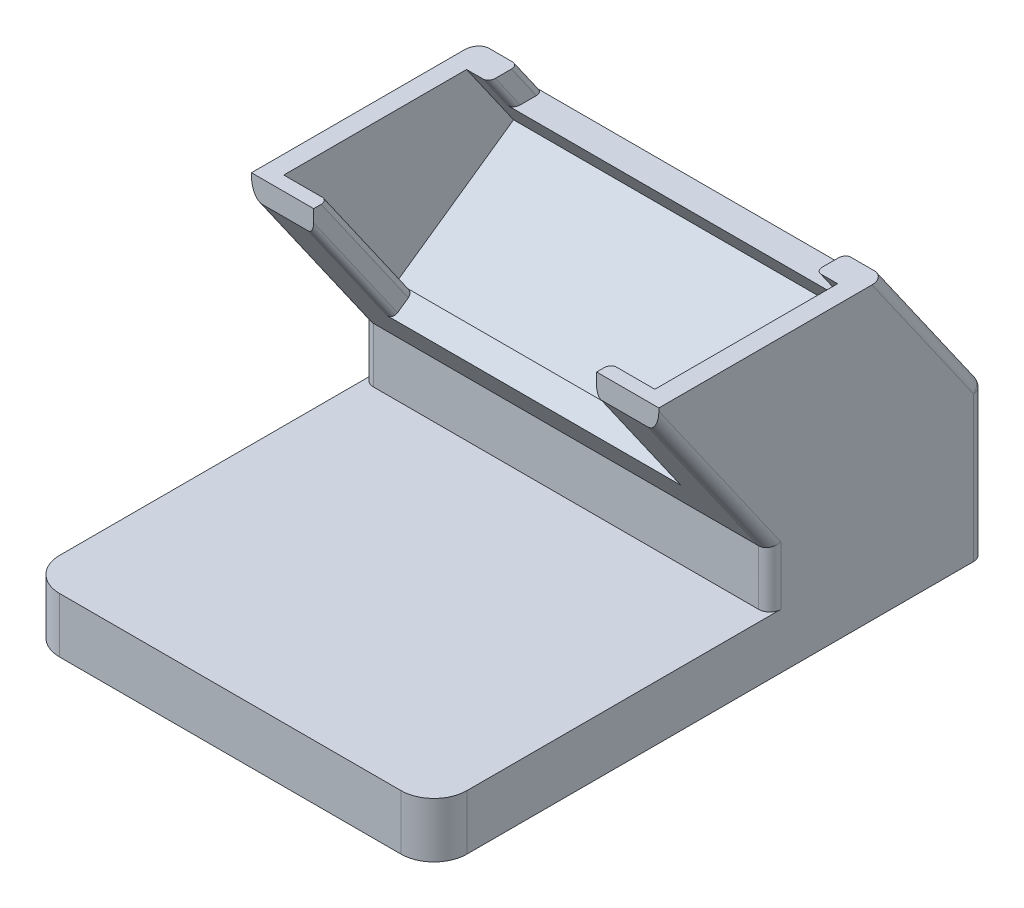
SolidWorks part; units mm, degrees
ref_plane "前视基准面" through (0, 0, 0) normal (0, 0, 1) x (1, 0, 0)
ref_plane "上视基准面" through (0, 0, 0) normal (0, 1, 0) x (1, 0, 0)
ref_plane "右视基准面" through (0, 0, 0) normal (1, 0, 0) x (0, 0, -1)
sketch "草图1" plane through (0, 0, 0) normal (1, 0, 0) x (0, 0, -1)
  line L0 (0, 0) -> (0, 5)
  line L1 (0, 5) -> (30.4974, 5)
  line L2 (30.4974, 5) -> (30.4974, 10)
  line L3 (30.4974, 10) -> (19.0259, 26.383)
  line L4 (19.0259, 26.383) -> (33.7706, 36.7074)
  line L5 (33.7706, 36.7074) -> (50, 13.5294)
  line L6 (50, 13.5294) -> (50, 0)
  line L7 (50, 0) -> (0, 0)
  dimension "D1" = 18
  dimension "D2" = 5
  dimension "D3" = 5
  dimension "D4" = 20
  dimension "D5" = 50
  dimension "D6" = 55
extrude "凸台-拉伸1" add sketch "草图1" along normal blind 37
sketch "草图2" plane through (0, 8.7641, 6.1367) normal (0, 0.8192, 0.5736) x (1, 0, 0)
  line L0 (18.5, 48.7178) -> (18.5, 30.7178) construction
  line L1 (37, 48.7178) -> (0, 48.7178) construction
  line L2 (37, 30.7178) -> (0, 30.7178) construction
  line L3 (0, 39.7178) -> (37, 39.7178) construction
  line L4 (0, 48.7178) -> (0, 30.7178) construction
  line L5 (37, 48.7178) -> (37, 30.7178) construction
  line L6 (33.35, 48.7178) -> (3.65, 48.7178)
  line L7 (3.65, 48.7178) -> (3.65, 46.5178)
  line L8 (3.65, 46.5178) -> (1.65, 46.5178)
  line L9 (1.65, 46.5178) -> (1.65, 32.9178)
  line L10 (1.65, 32.9178) -> (5.65, 32.9178)
  line L11 (5.65, 32.9178) -> (5.65, 30.7178)
  line L12 (37, 30.7178) -> (0, 30.7178) construction
  line L13 (5.65, 30.7178) -> (31.35, 30.7178)
  line L14 (31.35, 32.9178) -> (31.35, 30.7178)
  line L15 (35.35, 32.9178) -> (31.35, 32.9178)
  line L16 (33.35, 46.5178) -> (35.35, 46.5178)
  line L17 (35.35, 46.5178) -> (35.35, 32.9178)
  line L18 (33.35, 48.7178) -> (33.35, 46.5178)
  dimension "D1" = 13.6
  dimension "D2" = 2.2
  dimension "D3" = 2.2
  dimension "D4" = 33.7
  dimension "D5" = 4
  dimension "D6" = 2
extrude "切除-拉伸1" cut sketch "草图2" against normal blind 15
sketch "草图3" plane through (0, 0, 0) normal (-1, 0, 0) x (0, 0, 1)
  line L0 (-19.0259, 26.383) -> (-40.9998, 26.383)
  line L1 (-50, 13.5294) -> (-33.7706, 36.7074) construction
  line L2 (-40.9998, 26.383) -> (-33.7706, 36.7074)
  line L3 (-33.7706, 36.7074) -> (-19.0259, 26.383)
extrude "切除-拉伸2" cut sketch "草图3" against normal through all
sketch "草图4" plane through (0, -3.5232, -2.467) normal (0, 0.8192, 0.5736) x (1, 0, 0)
  line L1 (1.65, 46.5178) -> (35.35, 46.5178)
  line L2 (1.65, 46.5178) -> (1.65, 32.9178)
  line L3 (1.65, 32.9178) -> (35.35, 32.9178)
  line L4 (35.35, 46.5178) -> (35.35, 32.9178)
extrude "切除-拉伸3" cut sketch "草图4" against normal blind 3.5
sketch "草图5" plane through (33.35, 0, 0) normal (-1, 0, 0) x (0, 0, 1)
  line L0 (-40.5721, 23.1583) -> (-42.3743, 24.4201)
  line L1 (-40.5721, 23.1583) -> (-38.3141, 26.383) construction
  line L2 (-40.5721, 23.1583) -> (-42.3743, 24.4201) construction
  line L3 (-42.3743, 24.4201) -> (-43.2578, 23.1583)
  line L4 (-43.2578, 23.1583) -> (-40.5721, 23.1583)
extrude "切除-拉伸4" cut sketch "草图5" along normal up to surface (29.7 mm away) up to face at (3.65, 25.0861, -40.5651)
sketch "草图7" plane through (0, 27.9434, -39.9073) normal (0, 0.5736, -0.8192) x (-1, 0, 0)
  line L0 (-37, -17.1599) -> (0, -17.1599) construction
  line L1 (-37, -17.5962) -> (-37, -1.9048) construction
  line L2 (0, -17.5962) -> (0, -1.9048) construction
  text T0 "小电视" font "微软雅黑" height 3.5
sketch "草图8" plane through (37, 0, 0) normal (1, 0, 0) x (0, 0, -1)
  line L0 (19.0259, 26.383) -> (20.4259, 26.383)
  line L1 (40.9998, 26.383) -> (19.0259, 26.383) construction
  line L2 (20.4259, 26.383) -> (20.4259, 24.3836)
  line L3 (19.0259, 26.383) -> (30.4974, 10) construction
  line L4 (20.4259, 24.3836) -> (19.0259, 26.383)
  dimension "D1" = 1.4
extrude "切除-拉伸6" cut sketch "草图8" against normal through all
fillet "圆角1" radius 0.5 8 edges at (31.35, 19.2397, -24.0277) (31.35, 20.8703, -25.5716) (33.35, 24.7707, -39.4431) (33.35, 24.7707, -42.1288) (5.65, 19.2397, -24.0277) (5.65, 20.8703, -25.5716) (3.65, 24.7707, -39.4431) (3.65, 24.7707, -42.1288)
fillet "圆角2" radius 3 2 edges at (37, 2.5, 0) (0, 2.5, 0)
fillet "圆角3" radius 1 4 edges at (0, 19.9562, -45.4999) (37, 19.9562, -45.4999) (37, 17.1918, -25.4616) (0, 17.1918, -25.4616)
fillet "圆角4" radius 1 5 edges at (36.7071, 13.0188, -50) (18.5, 13.5294, -50) (0.2929, 13.0188, -50) (37, 5.893, -50) (0, 5.893, -50)
fillet "圆角5" radius 1 2 edges at (0, 8.3717, -30.4974) (37, 8.3717, -30.4974)
